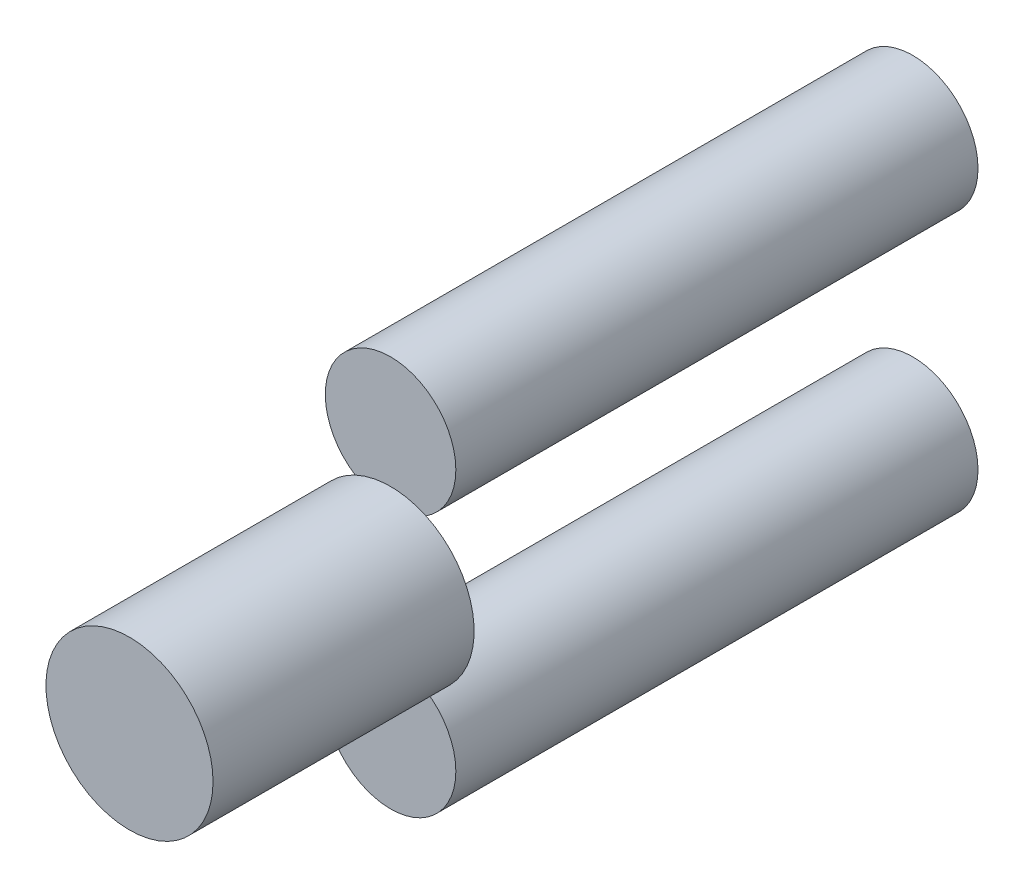
SolidWorks part; units mm, degrees
ref_plane "Front Plane" through (0, 0, 0) normal (0, 0, 1) x (1, 0, 0)
ref_plane "Top Plane" through (0, 0, 0) normal (0, 1, 0) x (1, 0, 0)
ref_plane "Right Plane" through (0, 0, 0) normal (1, 0, 0) x (0, 0, -1)
sketch "Sketch1" plane through (0, 0, 0) normal (0, 0, 1) x (1, 0, 0)
  line L0 (0, 0) -> (0, 19.05) construction
  circle A0 centre (0, 12.7) radius 1.5875
  circle A1 centre (0, 19.05) radius 1.5875
  dimension "D2" = 3.175
  dimension "D1" = 6.35
  dimension "D3" = 12.7
extrude "Boss-Extrude1" add sketch "Sketch1" against normal blind 12.7
sketch "Sketch2" plane through (0, 0, 0) normal (0, 0, 1) x (1, 0, 0)
  line L0 (0, 17.4625) -> (0, 14.2875) construction
  circle A0 centre (0, 15.875) radius 2.032
  circle A1 centre (0, 19.05) radius 1.5875 construction
  circle A2 centre (0, 12.7) radius 1.5875 construction
  dimension "D1" = 4.064
extrude "Boss-Extrude2" add sketch "Sketch2" along normal blind 6.35
ref_axis "Axis1" through (0, 15.875, 6.35) along (0, 0, -1)
equation "\"D1@Sketch1\"=2*0.125"
